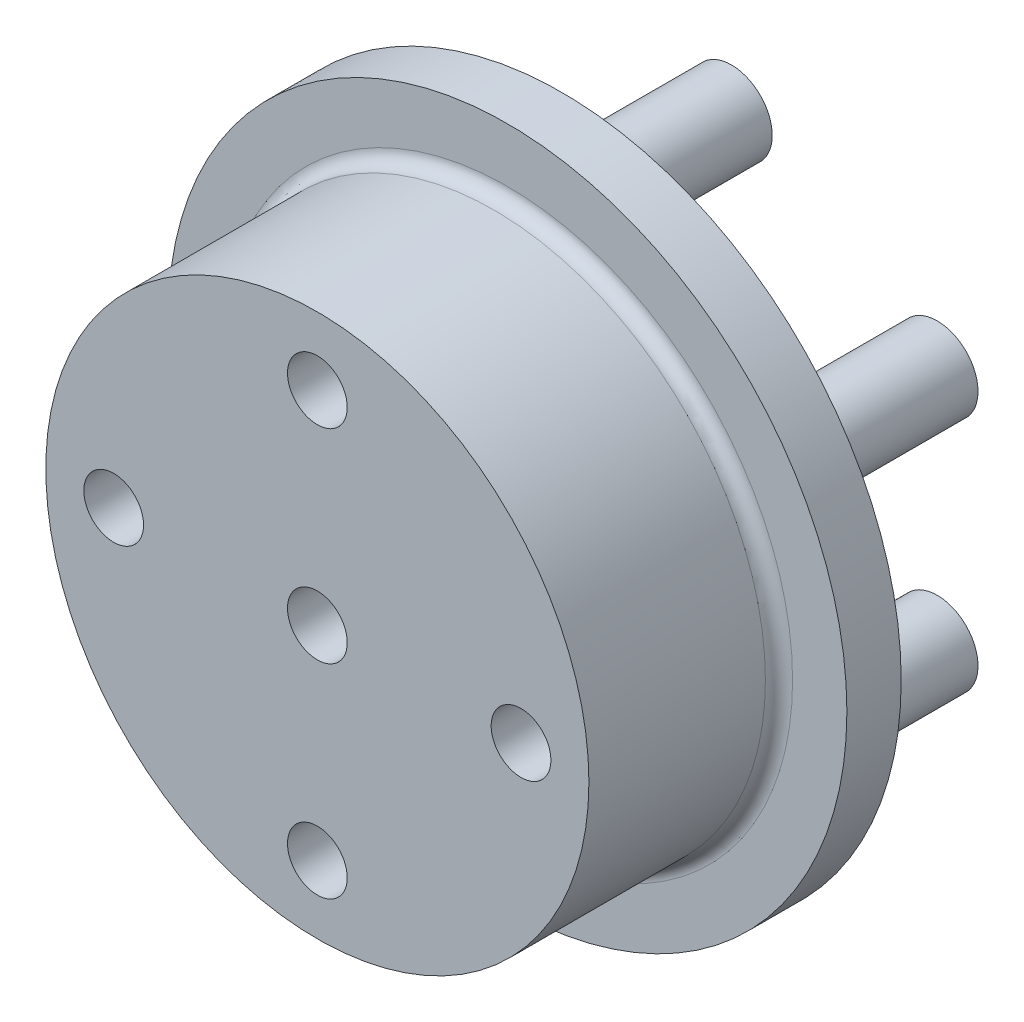
SolidWorks part; units mm, degrees
material "Polylactic Acid (PLA)"
ref_plane "Front Plane" through (0, 0, 0) normal (0, 0, 1) x (1, 0, 0)
ref_plane "Top Plane" through (0, 0, 0) normal (0, 1, 0) x (1, 0, 0)
ref_plane "Right Plane" through (0, 0, 0) normal (1, 0, 0) x (0, 0, -1)
sketch "Sketch1" plane through (0, 0, 0) normal (0, 0, 1) x (1, 0, 0)
  circle A0 centre (0, 0) radius 25
  circle A1 centre (0, 0) radius 15 construction
  dimension "D1" = 50
  dimension "D2" = 30
extrude "Boss-Extrude1" add sketch "Sketch1" against normal blind 4
sketch "Sketch2" plane through (0, 0, 0) normal (0, 0, 1) x (1, 0, 0)
  circle A0 centre (0, 0) radius 20
  dimension "D1" = 40
extrude "Boss-Extrude2" add sketch "Sketch2" along normal blind 14
fillet "Fillet1" radius 1 1 edges at (20, 0, 0)
sketch "Sketch3" plane through (0, 0, -4) normal (0, 0, -1) x (-1, 0, 0)
  circle A0 centre (0, 0) radius 10.2
  dimension "D1" = 20.4
extrude "Cut-Extrude1" cut sketch "Sketch3" against normal blind 5
sketch "Sketch4" plane through (0, 0, -4) normal (0, 0, -1) x (-1, 0, 0)
  circle A0 centre (0, 0) radius 17.5 construction
  circle A1 centre (0, 17.5) radius 3
  circle A2 centre (15.1554, 8.75) radius 3
  circle A3 centre (15.1554, -8.75) radius 3
  circle A4 centre (0, -17.5) radius 3
  circle A5 centre (-15.1554, -8.75) radius 3
  circle A6 centre (-15.1554, 8.75) radius 3
  circle A7 centre (0, 0) radius 10.2 construction
  point P17 (0, 0)
  dimension "D1" = 35
  dimension "D2" = 6
  dimension "D3" = 6
extrude "Boss-Extrude3" add sketch "Sketch4" along normal blind 12.5
sketch "Sketch7" plane through (0, 0, 14) normal (0, 0, 1) x (1, 0, 0)
  circle A0 centre (0, 0) radius 15 construction
  point P1 (0, 0)
  point P4 (0, 15)
  point P6 (15, 0)
  point P8 (0, -15)
  point P10 (-15, 0)
  dimension "D1" = 30
hole_wizard "Ø4.0mm Dowel Hole1" positions "Sketch7" profile "Sketch8" hole size "Ø4.0" standard "ISO"
sketch "Sketch8" plane through (0, 0, 14) normal (1, 0, 0) x (0, -1, 0)
  line L0 (0, 0) -> (0, 9.3219)
  line L1 (0, 9.3219) -> (2.2, 8)
  line L2 (2.2, 8) -> (2.2, 0)
  line L5 (2.2, 0) -> (0, 0)
  line L10 (0, 9.3219) -> (-2.2, 8) construction
  line L11 (0, -6.35) -> (0, 107.95) construction
  dimension "Hole Dia." = 4.4
  dimension "Hole Depth" = 8
  dimension "Drill Angle" = 118
